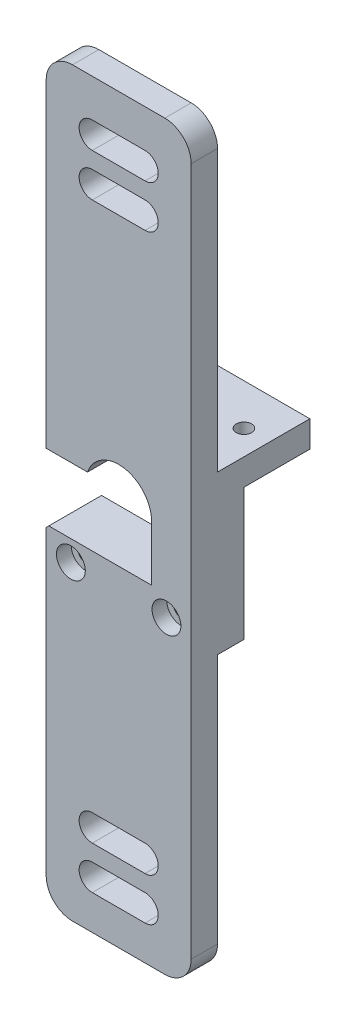
SolidWorks part; units mm, degrees
material "ABS"
ref_plane "Front Plane" through (0, 0, 0) normal (0, 0, 1) x (1, 0, 0)
ref_plane "Top Plane" through (0, 0, 0) normal (0, 1, 0) x (1, 0, 0)
ref_plane "Right Plane" through (0, 0, 0) normal (1, 0, 0) x (0, 0, -1)
ref_plane "Plane1" through (0, 0, 33.655) normal (0, 0, 1) x (1, 0, 0)
sketch "Sketch1" plane through (0, 0, 33.655) normal (0, 0, 1) x (1, 0, 0)
  line L0 (-13.97, 9.8105) -> (-13.462, 9.8105)
  line L1 (-13.462, 9.8105) -> (-13.462, 10.3185)
  line L2 (-13.462, 10.3185) -> (-13.97, 9.8105)
extrude "Boss-Extrude1" add sketch "Sketch1" against normal blind 5.08
sketch "Sketch2" plane through (-13.462, 0, 0) normal (1, 0, 0) x (0, 0, -1)
  line L0 (-33.655, 10.3185) -> (-28.575, 10.3185)
  line L1 (-28.575, 10.3185) -> (-28.575, 9.8105)
  line L2 (-28.575, 9.8105) -> (-33.655, 9.8105)
  line L3 (-33.655, 9.8105) -> (-33.655, 10.3185)
extrude "Boss-Extrude2" add sketch "Sketch2" along normal blind 17.907
sketch "Sketch3" plane through (4.445, 0, 0) normal (1, 0, 0) x (0, 0, -1)
  line L0 (-28.575, 9.8105) -> (-33.655, 9.8105)
  line L1 (-33.655, 9.8105) -> (-33.655, 10.3185)
  line L2 (-33.655, 10.3185) -> (-29.083, 10.3185)
  line L3 (-29.083, 10.3185) -> (-28.575, 10.8265)
  line L4 (-28.575, 10.8265) -> (-28.575, 9.8105)
extrude "Boss-Extrude3" add sketch "Sketch3" along normal blind 1.905
sketch "Sketch4" plane through (0, 0, 28.575) normal (0, 0, -1) x (-1, 0, 0)
  line L0 (-6.35, 9.8105) -> (-6.35, 27.303)
  line L1 (-6.35, 27.303) -> (3.937, 27.303)
  line L2 (3.937, 27.303) -> (3.937, 23.0185)
  line L3 (-3.937, 23.0185) -> (-4.445, 23.0185)
  line L4 (-4.445, 23.0185) -> (-4.445, 10.3185)
  line L5 (-4.445, 10.3185) -> (13.462, 10.3185)
  line L6 (13.462, 10.3185) -> (13.97, 9.8105)
  line L7 (13.97, 9.8105) -> (-6.35, 9.8105)
  arc A0 (3.937, 23.0185) -> (-3.937, 23.0185) centre (0, 20.955) ccw
extrude "Boss-Extrude4" add sketch "Sketch4" along normal blind 17.78
sketch "Sketch5" plane through (0, 9.8105, 0) normal (0, -1, 0) x (1, 0, 0)
  line L0 (6.35, 10.795) -> (-13.97, 10.795)
  line L1 (-13.97, 10.795) -> (-13.97, 33.655)
  line L2 (-13.97, 33.655) -> (6.35, 33.655)
  line L3 (6.35, 33.655) -> (6.35, 10.795)
extrude "Boss-Extrude5" add sketch "Sketch5" along normal blind 63.1505
sketch "Sketch6" plane through (-3.937, 0, 0) normal (-1, 0, 0) x (0, 0, 1)
  line L0 (28.575, 23.0185) -> (10.795, 23.0185)
  line L1 (10.795, 23.0185) -> (10.795, 27.303)
  line L2 (10.795, 27.303) -> (28.575, 27.303)
  line L3 (28.575, 27.303) -> (28.575, 23.0185)
extrude "Boss-Extrude6" add sketch "Sketch6" along normal blind 10.033
sketch "Sketch7" plane through (0, 0, 28.575) normal (0, 0, 1) x (1, 0, 0)
  line L0 (0.1584, 27.303) -> (6.35, 27.303)
  line L1 (6.35, 27.303) -> (6.35, 20.955)
  arc A0 (6.35, 20.955) -> (0.1584, 27.303) centre (0, 20.955) ccw
extrude "Boss-Extrude7" add sketch "Sketch7" along normal blind 5.08
sketch "Sketch8" plane through (6.35, 0, 0) normal (1, 0, 0) x (0, 0, -1)
  line L0 (-10.795, 27.303) -> (-10.795, -53.34)
  line L1 (-10.795, -53.34) -> (-33.655, -53.34)
  line L2 (-33.655, -53.34) -> (-33.655, 27.303)
  line L3 (-33.655, 27.303) -> (-10.795, 27.303)
extrude "Boss-Extrude8" add sketch "Sketch8" along normal blind 7.62
sketch "Sketch9" plane through (0, 0, 10.795) normal (0, 0, -1) x (-1, 0, 0)
  line L0 (13.97, 25.4) -> (4.445, 25.4)
  line L1 (4.445, 25.4) -> (4.445, 23.5265)
  line L2 (4.445, 23.5265) -> (3.937, 23.0185)
  line L3 (3.937, 23.0185) -> (13.97, 23.0185)
  line L4 (13.97, 23.0185) -> (13.97, 25.4)
extrude "Cut-Extrude1" cut sketch "Sketch9" against normal blind 12.7
sketch "Sketch10" plane through (0, 0, 10.795) normal (0, 0, -1) x (-1, 0, 0)
  line L0 (-4.445, 10.3185) -> (-4.445, 23.0185)
  line L1 (-4.445, 23.0185) -> (-13.97, 23.0185)
  line L2 (-13.97, 23.0185) -> (-13.97, -53.34)
  line L3 (-13.97, -53.34) -> (13.97, -53.34)
  line L4 (13.97, -53.34) -> (13.97, 9.8105)
  line L5 (13.97, 9.8105) -> (13.462, 10.3185)
  line L6 (13.462, 10.3185) -> (-4.445, 10.3185)
extrude "Cut-Extrude2" cut sketch "Sketch10" against normal blind 12.7
sketch "Sketch11" plane through (0, 0, 28.575) normal (0, 0, 1) x (1, 0, 0)
  line L0 (-6.0054, 23.0185) -> (-13.97, 23.0185)
  line L1 (-13.97, 23.0185) -> (-13.97, 27.303)
  line L2 (-13.97, 27.303) -> (-0.1584, 27.303)
  arc A0 (-0.1584, 27.303) -> (-6.0054, 23.0185) centre (0, 20.955) ccw
extrude "Boss-Extrude9" add sketch "Sketch11" along normal blind 5.08
sketch "Sketch12" plane through (0, 27.303, 0) normal (0, 1, 0) x (-1, 0, 0)
  line L0 (-13.97, 33.655) -> (13.97, 33.655)
  line L1 (13.97, 33.655) -> (13.97, 10.795)
  line L2 (13.97, 10.795) -> (-13.97, 10.795)
  line L3 (-13.97, 10.795) -> (-13.97, 33.655)
extrude "Boss-Extrude10" add sketch "Sketch12" along normal blind 62.232
sketch "Sketch13" plane through (0, 23.0185, 0) normal (0, -1, 0) x (1, 0, 0)
  line L0 (13.97, 10.795) -> (13.97, 23.495)
  line L1 (13.97, 23.495) -> (4.445, 23.495)
  line L2 (4.445, 23.495) -> (4.445, 10.795)
  line L3 (4.445, 10.795) -> (13.97, 10.795)
extrude "Cut-Extrude3" cut sketch "Sketch13" against normal blind 2.3815
sketch "Sketch14" plane through (13.97, 0, 0) normal (1, 0, 0) x (0, 0, -1)
  line L0 (-28.575, 30.48) -> (-10.795, 30.48)
  line L1 (-10.795, 30.48) -> (-10.795, 89.535)
  line L2 (-10.795, 89.535) -> (-28.575, 89.535)
  line L3 (-28.575, 89.535) -> (-28.575, 30.48)
extrude "Cut-Extrude4" cut sketch "Sketch14" against normal through all
sketch "Sketch15" plane through (13.97, 0, 0) normal (1, 0, 0) x (0, 0, -1)
  line L0 (-23.495, 0) -> (-28.575, 0)
  line L1 (-28.575, 0) -> (-28.575, -53.34)
  line L2 (-28.575, -53.34) -> (-23.495, -53.34)
  line L3 (-23.495, -53.34) -> (-23.495, 0)
extrude "Cut-Extrude5" cut sketch "Sketch15" against normal through all
sketch "Sketch16" plane through (0, 0, 28.575) normal (0, 0, -1) x (-1, 0, 0)
  line L0 (5.08, -41.5925) -> (-5.08, -41.5925)
  line L1 (-5.08, -46.6725) -> (5.08, -46.6725)
  arc A0 (5.08, -46.6725) -> (5.08, -41.5925) centre (5.08, -44.1325) ccw
  arc A1 (-5.08, -41.5925) -> (-5.08, -46.6725) centre (-5.08, -44.1325) ccw
extrude "Cut-Extrude6" cut sketch "Sketch16" against normal through all
sketch "Sketch17" plane through (0, 0, 33.655) normal (0, 0, 1) x (1, 0, 0)
  line L0 (-5.08, -38.4175) -> (5.08, -38.4175)
  line L1 (5.08, -33.3375) -> (-5.08, -33.3375)
  arc A0 (5.08, -38.4175) -> (5.08, -33.3375) centre (5.08, -35.8775) ccw
  arc A1 (-5.08, -33.3375) -> (-5.08, -38.4175) centre (-5.08, -35.8775) ccw
extrude "Cut-Extrude7" cut sketch "Sketch17" against normal through all
sketch "Sketch18" plane through (0, 0, 28.575) normal (0, 0, -1) x (-1, 0, 0)
  line L0 (5.08, 73.9775) -> (-5.08, 73.9775)
  line L1 (-5.08, 68.8975) -> (5.08, 68.8975)
  arc A0 (5.08, 68.8975) -> (5.08, 73.9775) centre (5.08, 71.4375) ccw
  arc A1 (-5.08, 73.9775) -> (-5.08, 68.8975) centre (-5.08, 71.4375) ccw
extrude "Cut-Extrude8" cut sketch "Sketch18" against normal through all
sketch "Sketch19" plane through (0, 0, 28.575) normal (0, 0, -1) x (-1, 0, 0)
  line L0 (5.08, 82.2325) -> (-5.08, 82.2325)
  line L1 (-5.08, 77.1525) -> (5.08, 77.1525)
  arc A0 (5.08, 77.1525) -> (5.08, 82.2325) centre (5.08, 79.6925) ccw
  arc A1 (-5.08, 82.2325) -> (-5.08, 77.1525) centre (-5.08, 79.6925) ccw
extrude "Cut-Extrude9" cut sketch "Sketch19" against normal through all
hole_wizard "CBORE for M2.5 Hex Head Machine Screw1" positions "Sketch21" profile "Sketch20" counterbore size "M2.5" standard "ANSI Metric"
sketch "Sketch21" plane through (0, 0, 33.655) normal (0, 0, 1) x (1, 0, 0)
  point P0 (9.2075, 6.35)
  point P1 (-9.2075, 6.35)
sketch "Sketch20" plane through (9.2075, 6.35, 33.655) normal (1, 0, 0) x (0, -1, 0)
  line L0 (0, 0) -> (0, 22.86)
  line L1 (0, 22.86) -> (1.4732, 22.86)
  line L3 (1.4732, 22.86) -> (1.4732, 2.8448)
  line L4 (1.4732, 2.8448) -> (2.7788, 2.8448)
  line L5 (2.7788, 2.8448) -> (2.7788, 0)
  line L7 (2.7788, 0) -> (0, 0)
  line L11 (0, -6.35) -> (0, 107.95) construction
  dimension "Thru Hole Dia." = 2.9464
  dimension "Thru Hole Depth" = 22.86
  dimension "C'Bore Dia." = 5.5575
  dimension "C'Bore Depth" = 2.8448
hole_wizard "M2.5 Clearance Hole1" positions "Sketch23" profile "Sketch22" hole size "M2.5" standard "ANSI Metric"
sketch "Sketch23" plane through (0, 30.48, 0) normal (0, 1, 0) x (1, 0, 0)
  point P0 (9.2075, -18.7325)
sketch "Sketch22" plane through (9.2075, 30.48, 18.7325) normal (1, 0, 0) x (0, 0, 1)
  line L0 (0, 0) -> (0, 83.82)
  line L1 (0, 83.82) -> (1.4732, 83.82)
  line L2 (1.4732, 83.82) -> (1.4732, 0)
  line L5 (1.4732, 0) -> (0, 0)
  line L11 (0, -6.35) -> (0, 107.95) construction
  dimension "Thru Hole Dia." = 2.9464
  dimension "Thru Hole Depth" = 83.82
hole_wizard "M2.5 Clearance Hole2" positions "Sketch25" profile "Sketch24" hole size "M2.5" standard "ANSI Metric"
sketch "Sketch25" plane through (0, 25.4, 0) normal (0, -1, 0) x (-1, 0, 0)
  point P0 (9.2075, -18.7325)
sketch "Sketch24" plane through (-9.2075, 25.4, 18.7325) normal (1, 0, 0) x (0, 0, -1)
  line L0 (0, 0) -> (0, 64.135)
  line L1 (0, 64.135) -> (1.4732, 64.135)
  line L2 (1.4732, 64.135) -> (1.4732, 0)
  line L5 (1.4732, 0) -> (0, 0)
  line L11 (0, -6.35) -> (0, 107.95) construction
  dimension "Thru Hole Dia." = 2.9464
  dimension "Thru Hole Depth" = 64.135
fillet "Fillet2" radius 2.54 1 edges at (4.445, 10.3185, 26.289) tangent propagation no
chamfer "Chamfer2" distance 0.938 angle 45 2 edges at (4.5458, 25.3888, 28.575) (6.35, 15.8908, 28.575)
fillet "Fillet3" radius 5.08 4 edges at (13.97, -53.34, 31.115) (-13.97, -53.34, 31.115) (13.97, 89.535, 31.115) (-13.97, 89.535, 31.115) tangent propagation no
